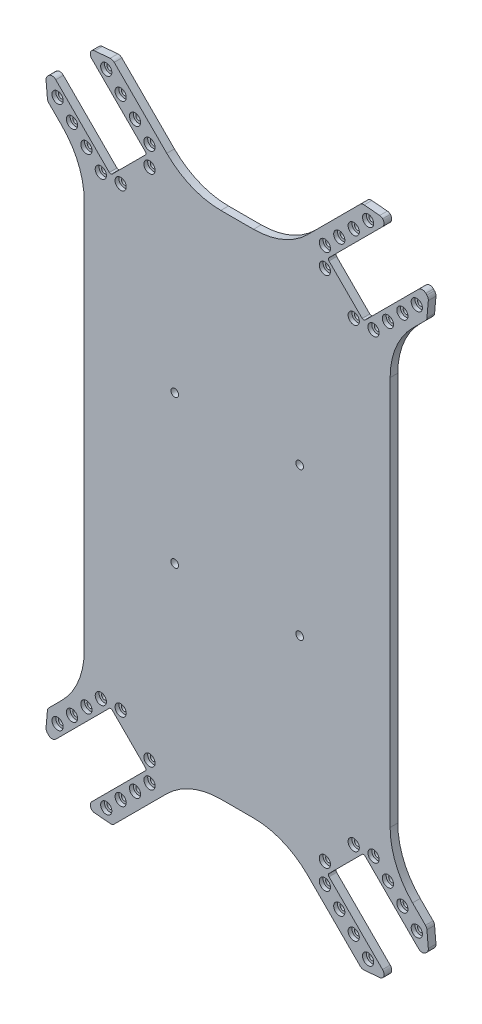
SolidWorks part; units mm, degrees
material "ABS"
ref_plane "Front Plane" through (0, 0, 0) normal (0, 0, 1) x (1, 0, 0)
ref_plane "Top Plane" through (0, 0, 0) normal (0, 1, 0) x (1, 0, 0)
ref_plane "Right Plane" through (0, 0, 0) normal (1, 0, 0) x (0, 0, -1)
sketch "Sketch1" plane through (0, 0, 0) normal (0, 0, 1) x (1, 0, 0)
  line L1 (0, 0) -> (-60, 0)
  line L2 (0, 0) -> (0, 100)
  line L3 (0, 100) -> (-60, 100)
  line L4 (-60, 0) -> (-60, 100)
  dimension "D1" = 100
  dimension "D2" = 60
sketch "Sketch2" plane through (0, 0, 0) normal (0, 0, 1) x (1, 0, 0)
  line L0 (-85.6588, 114.4959) -> (-51.3641, 80.2012)
  line L1 (-85.6588, 114.4959) -> (-59.4959, 140.6588)
  line L2 (-51.3641, 80.2012) -> (-25.2012, 106.3641)
  line L3 (-59.4959, 140.6588) -> (-25.2012, 106.3641)
  line L4 (-85.6588, 114.4959) -> (-25.2012, 106.3641) construction
  line L5 (-51.3641, 80.2012) -> (-59.4959, 140.6588) construction
  line L6 (0, 100) -> (-60, 100) construction
  line L7 (0, 0) -> (0, 100) construction
  line L8 (-52.4248, 133.5877) -> (-78.5877, 107.4248) construction
  point P1 (-55.43, 110.43)
  dimension "D1" = 135
  dimension "D2" = 37
  dimension "D3" = 48.5
  dimension "D4" = 55.43
  dimension "D5" = 10.43
  dimension "D6" = 38.5
sketch "Sketch4" plane through (0, 0, 0) normal (0, 0, 1) x (1, 0, 0)
  line L0 (-75.4058, 116.2636) -> (-49.5964, 90.4542)
  line L1 (-75.4058, 116.2636) -> (-61.2636, 130.4058)
  line L2 (-49.5964, 90.4542) -> (-35.4542, 104.5964)
  line L3 (-61.2636, 130.4058) -> (-35.4542, 104.5964)
  line L4 (-75.4058, 116.2636) -> (-35.4542, 104.5964) construction
  line L5 (-49.5964, 90.4542) -> (-61.2636, 130.4058) construction
  line L7 (-51.3641, 80.2012) -> (-25.2012, 106.3641) construction
  point P1 (-55.43, 110.43)
  dimension "D1" = 20
  dimension "D2" = 6
sketch "Sketch6" plane through (0, 0, 0) normal (0, 0, 1) x (1, 0, 0)
  line L0 (-70.456, 106.3641) -> (-35.3409, 71.249) construction
  line L1 (-75.4058, 116.2636) -> (-49.5964, 90.4542) construction
  line L2 (-52.4248, 133.5877) -> (-78.5877, 107.4248) construction
  line L3 (-55.43, 110.43) -> (-38.2827, 93.2827) construction
  line L4 (-51.3641, 80.2012) -> (-25.2012, 106.3641) construction
  line L5 (-51.3641, 125.456) -> (-16.249, 90.3409) construction
  point P0 (-70.456, 106.3641)
  point P1 (-64.7992, 100.7073)
  point P2 (-59.1423, 95.0504)
  point P3 (-53.4855, 89.3936)
  point P4 (-45.7073, 89.3936)
  point P16 (-34.3936, 100.7073)
  point P17 (-34.3936, 108.4855)
  point P18 (-40.0504, 114.1423)
  point P21 (-45.7073, 119.7992)
  dimension "D1" = 6.5
  dimension "D2" = 8
  dimension "D3" = 8
  dimension "D4" = 8
  dimension "D5" = 13.5
  dimension "D6" = 8
  dimension "D7" = 36
sketch "Sketch9" [suppressed] plane through (0, 0, 0) normal (0, 0, 1) x (1, 0, 0)
  line L0 (-55.43, 105.43) -> (-38.2827, 88.2827) construction
  line L1 (-61.8582, 90.645) -> (-39.5695, 68.3563) construction
  line L2 (-77.315, 109.9201) -> (-50.9399, 83.545) construction
  line L3 (-52.4955, 128.6585) -> (-78.6585, 102.4955) construction
  line L4 (-40.645, 111.8582) -> (-18.3563, 89.5695) construction
  point P8 (-67.3447, 96.1315)
  point P9 (-55.3239, 84.1107)
  point P10 (-46.273, 84.2522)
  point P13 (-34.2522, 96.273)
  point P14 (-34.1107, 105.3239)
  point P15 (-46.1315, 117.3447)
  dimension "D1" = 15
  dimension "D2" = 12.5
  dimension "D3" = 17
  dimension "D4" = 8.5
  dimension "D5" = 35.8
sketch "Sketch15" plane through (0, 0, 0) normal (0, 0, 1) x (1, 0, 0)
  line L0 (-51.3641, 80.2012) -> (-25.2012, 106.3641) construction
  line L1 (-31.18, -18.5) -> (-79.68, -18.5)
  line L2 (-31.18, -18.5) -> (-31.18, 18.5)
  line L3 (-31.18, 18.5) -> (-79.68, 18.5)
  line L4 (-79.68, -18.5) -> (-79.68, 18.5)
  line L5 (-31.18, -18.5) -> (-79.68, 18.5) construction
  line L6 (-31.18, 18.5) -> (-79.68, -18.5) construction
  line L7 (-85.6588, 114.4959) -> (-51.3641, 80.2012) construction
  line L9 (-69.78, 18.5) -> (-69.78, -18.5) construction
  line L12 (-75.4058, 116.2636) -> (-49.5964, 90.4542) construction
  line L13 (-37.18, -10) -> (-73.68, -10)
  line L14 (-37.18, -10) -> (-37.18, 10)
  line L15 (-37.18, 10) -> (-73.68, 10)
  line L16 (-73.68, -10) -> (-73.68, 10)
  line L17 (-37.18, -10) -> (-73.68, 10) construction
  line L18 (-37.18, 10) -> (-73.68, -10) construction
  line L19 (-49.5964, 90.4542) -> (-35.4542, 104.5964) construction
  point P0 (-55.43, 0)
  point P12 (-55.43, 0)
  dimension "D1" = 38.6
sketch "Sketch18" [suppressed] plane through (0, 0, 0) normal (0, 0, 1) x (1, 0, 0)
  line L0 (-63.4757, 15) -> (-37.4054, 15) construction
  line L1 (-69.78, 18.5) -> (-69.78, -18.5) construction
  point P2 (-57.28, 15)
  point P3 (-40.28, 15)
  point P4 (-33.98, 8.5)
  dimension "D1" = 12.5
  dimension "D2" = 17
  dimension "D3" = 15
  dimension "D4" = 8.5
  dimension "D5" = 35.8
sketch "Sketch22" [suppressed] plane through (0, 0, 0) normal (0, 0, 1) x (1, 0, 0)
  line L0 (-68.7515, 13.5) -> (-41.8085, 13.5) construction
  line L1 (-69.78, 18.5) -> (-69.78, -18.5) construction
  point P2 (-63.28, 13.5)
  point P3 (-55.28, 13.5)
  point P4 (-47.28, 13.5)
  point P5 (-39.28, 13.5)
  point P6 (-33.78, 8)
  dimension "D1" = 6.5
  dimension "D2" = 8
  dimension "D3" = 8
  dimension "D4" = 8
  dimension "D5" = 8
  dimension "D6" = 36
  dimension "D7" = 13.5
sketch "Sketch3" plane through (0, 0, 0) normal (0, 0, 1) x (1, 0, 0)
  line L0 (-52.4248, 133.5877) -> (-78.5877, 107.4248)
  line L1 (-78.5877, 107.4248) -> (-60, 88.837)
  line L2 (-60, 0) -> (-60, 100) construction
  line L3 (-60, 88.837) -> (-60, 0)
  line L4 (-60, 0) -> (0, 0)
  line L5 (0, 0) -> (0, 100)
  line L6 (-52.4248, 133.5877) -> (-18.837, 100)
  line L7 (0, 100) -> (-60, 100) construction
  line L8 (-18.837, 100) -> (0, 100)
  line L9 (-59.4959, 140.6588) -> (-25.2012, 106.3641) construction
extrude "Boss-Extrude1" add sketch "Sketch3" along normal blind 3
sketch "Sketch5" plane through (0, 0, 3) normal (0, 0, 1) x (1, 0, 0)
  line L0 (-35.4542, 104.5964) -> (-49.5964, 90.4542)
  line L1 (-49.5964, 90.4542) -> (-75.4058, 116.2636)
  line L2 (-75.4058, 116.2636) -> (-61.2636, 130.4058)
  line L3 (-61.2636, 130.4058) -> (-35.4542, 104.5964)
extrude "Cut-Extrude1" cut sketch "Sketch5" against normal through all
hole_wizard "CBORE for M2 Hex Socket Head Cap Screw2" [suppressed] positions "Sketch11" profile "Sketch10" counterbore size "M2" standard "ISO"
sketch "Sketch11" plane through (0, 0, 3) normal (0, 0, 1) x (1, 0, 0)
  point P0 (-67.3447, 96.1315)
  point P3 (-55.3239, 84.1107)
  point P6 (-46.273, 84.2522)
  point P9 (-34.2522, 96.273)
  point P12 (-34.1107, 105.3239)
  point P15 (-46.1315, 117.3447)
sketch "Sketch10" plane through (-67.3447, 96.1315, 3) normal (1, 0, 0) x (0, -1, 0)
  line L0 (0, 0) -> (0, 3)
  line L1 (0, 3) -> (1.2, 3)
  line L3 (1.2, 3) -> (1.2, 1.5)
  line L4 (1.2, 1.5) -> (2.2, 1.5)
  line L5 (2.2, 1.5) -> (2.2, 0)
  line L7 (2.2, 0) -> (0, 0)
  line L11 (0, -6.35) -> (0, 107.95) construction
  dimension "Thru Hole Dia." = 2.4
  dimension "Thru Hole Depth" = 3
  dimension "C'Bore Dia." = 4.4
  dimension "C'Bore Depth" = 1.5
hole_wizard "CBORE for M2 Hex Socket Head Cap Screw3" positions "Sketch13" profile "Sketch12" counterbore size "M2" standard "ISO" end condition through all
sketch "Sketch13" plane through (0, 0, 3) normal (0, 0, 1) x (1, 0, 0)
  point P0 (-70.456, 106.3641)
  point P3 (-64.7992, 100.7073)
  point P6 (-59.1423, 95.0504)
  point P9 (-53.4855, 89.3936)
  point P12 (-45.7073, 89.3936)
  point P15 (-34.3936, 100.7073)
  point P18 (-34.3936, 108.4855)
  point P21 (-40.0504, 114.1423)
  point P24 (-45.7073, 119.7992)
  point P27 (-51.3641, 125.456)
sketch "Sketch12" plane through (-70.456, 106.3641, 3) normal (1, 0, 0) x (0, -1, 0)
  line L0 (0, 0) -> (0, 3)
  line L1 (0, 3) -> (1.2, 3)
  line L3 (1.2, 3) -> (1.2, 1.5)
  line L4 (1.2, 1.5) -> (2.2, 1.5)
  line L5 (2.2, 1.5) -> (2.2, 0)
  line L7 (2.2, 0) -> (0, 0)
  line L11 (0, -6.35) -> (0, 107.95) construction
  dimension "Thru Hole Dia." = 2.4
  dimension "Thru Hole Depth" = 3
  dimension "C'Bore Dia." = 4.4
  dimension "C'Bore Depth" = 1.5
sketch "Sketch16" plane through (0, 0, 3) normal (0, 0, 1) x (1, 0, 0)
  line L0 (-60, 18.5) -> (-69.78, 18.5)
  line L1 (-31.18, 18.5) -> (-79.68, 18.5) construction
  line L2 (-60, 88.837) -> (-60, 0) construction
  line L3 (-69.78, 18.5) -> (-69.78, 10)
  line L4 (-37.18, 10) -> (-73.68, 10) construction
  line L5 (-69.78, 18.5) -> (-69.78, -18.5) construction
  line L6 (-69.78, 10) -> (-60, 10)
  line L7 (-60, 10) -> (-60, 18.5)
extrude "Boss-Extrude2" [suppressed] add sketch "Sketch16" against normal up to surface (3 mm away)
sketch "Sketch21" [suppressed] plane through (0, 0, 3) normal (0, 0, 1) x (1, 0, 0)
  line L0 (-50, 10) -> (-50, 0)
  line L1 (-50, 0) -> (-37.18, 0)
  line L2 (-37.18, -10) -> (-37.18, 10) construction
  line L3 (-37.18, 0) -> (-37.18, 10)
  line L4 (-37.18, 10) -> (-50, 10)
extrude "Cut-Extrude3" [suppressed] cut sketch "Sketch21" against normal up to next
sketch "Sketch14" plane through (0, 0, 3) normal (0, 0, 1) x (1, 0, 0)
  line L0 (-60, 0) -> (0, 0) construction
  line L1 (0, 0) -> (0, 100) construction
  circle A0 centre (-24.5, 29) radius 1.5
  dimension "D1" = 3
  dimension "D2" = 29
  dimension "D3" = 24.5
extrude "Cut-Extrude2" cut sketch "Sketch14" against normal through all
hole_wizard "CBORE for M2 Hex Socket Head Cap Screw4" [suppressed] positions "Sketch20" profile "Sketch19" counterbore size "M2" standard "ISO"
sketch "Sketch20" [suppressed] plane through (0, 0, 3) normal (0, 0, 1) x (1, 0, 0)
  point P0 (-57.28, 15)
  point P3 (-40.28, 15)
  point P6 (-33.98, 8.5)
sketch "Sketch19" plane through (-57.28, 15, 3) normal (1, 0, 0) x (0, -1, 0)
  line L0 (0, 0) -> (0, 3)
  line L1 (0, 3) -> (1.2, 3)
  line L3 (1.2, 3) -> (1.2, 1.5)
  line L4 (1.2, 1.5) -> (2.2, 1.5)
  line L5 (2.2, 1.5) -> (2.2, 0)
  line L7 (2.2, 0) -> (0, 0)
  line L11 (0, -6.35) -> (0, 107.95) construction
  dimension "Thru Hole Dia." = 2.4
  dimension "Thru Hole Depth" = 3
  dimension "C'Bore Dia." = 4.4
  dimension "C'Bore Depth" = 1.5
hole_wizard "CBORE for M2 Hex Socket Head Cap Screw5" [suppressed] positions "Sketch24" profile "Sketch23" counterbore size "M2" standard "ISO"
sketch "Sketch24" [suppressed] plane through (0, 0, 3) normal (0, 0, 1) x (1, 0, 0)
  point P0 (-63.28, 13.5)
  point P3 (-55.28, 13.5)
  point P6 (-47.28, 13.5)
  point P9 (-39.28, 13.5)
  point P12 (-33.78, 8)
sketch "Sketch23" plane through (-63.28, 13.5, 3) normal (1, 0, 0) x (0, -1, 0)
  line L0 (0, 0) -> (0, 3)
  line L1 (0, 3) -> (1.2, 3)
  line L3 (1.2, 3) -> (1.2, 1.5)
  line L4 (1.2, 1.5) -> (2.2, 1.5)
  line L5 (2.2, 1.5) -> (2.2, 0)
  line L7 (2.2, 0) -> (0, 0)
  line L11 (0, -6.35) -> (0, 107.95) construction
  dimension "Thru Hole Dia." = 2.4
  dimension "Thru Hole Depth" = 3
  dimension "C'Bore Dia." = 4.4
  dimension "C'Bore Depth" = 1.5
fillet "Fillet1" radius 30 2 edges at (-60, 88.837, 1.5) (-18.837, 100, 1.5)
chamfer "Chamfer1" distance 5 angle 50 2 edges at (-52.4248, 133.5877, 1.5) (-78.5877, 107.4248, 1.5) first distance on face at (-40.0243, 121.1873, 1.5) first distance on face at (-75.5825, 110.43, 1.5)
fillet "Fillet2" radius 2 6 edges at (-74.3743, 103.2113, 1.5) (-75.0522, 110.9603, 1.5) (-56.6383, 129.3743, 1.5) (-48.8893, 130.0522, 1.5) (-72.5773, 113.4352, 1.5) (-58.4352, 127.5773, 1.5)
fillet "Fillet3" radius 0.8 2 edges at (-49.5964, 90.4542, 1.5) (-35.4542, 104.5964, 1.5)
chamfer "Chamfer2" [suppressed] distance 5 angle 45
fillet "Fillet5" [suppressed] radius 5
fillet "Fillet6" [suppressed] radius 1
fillet "Fillet7" [suppressed] radius 1
fillet "Fillet8" [suppressed] radius 0.8
fillet "Fillet4" [suppressed] radius 20
mirror "Mirror1" about plane through (0, 0, 0) normal (1, 0, 0) of bodies 108 103
mirror "Mirror2" about plane through (0, 0, 0) normal (0, 1, 0) of bodies 104
